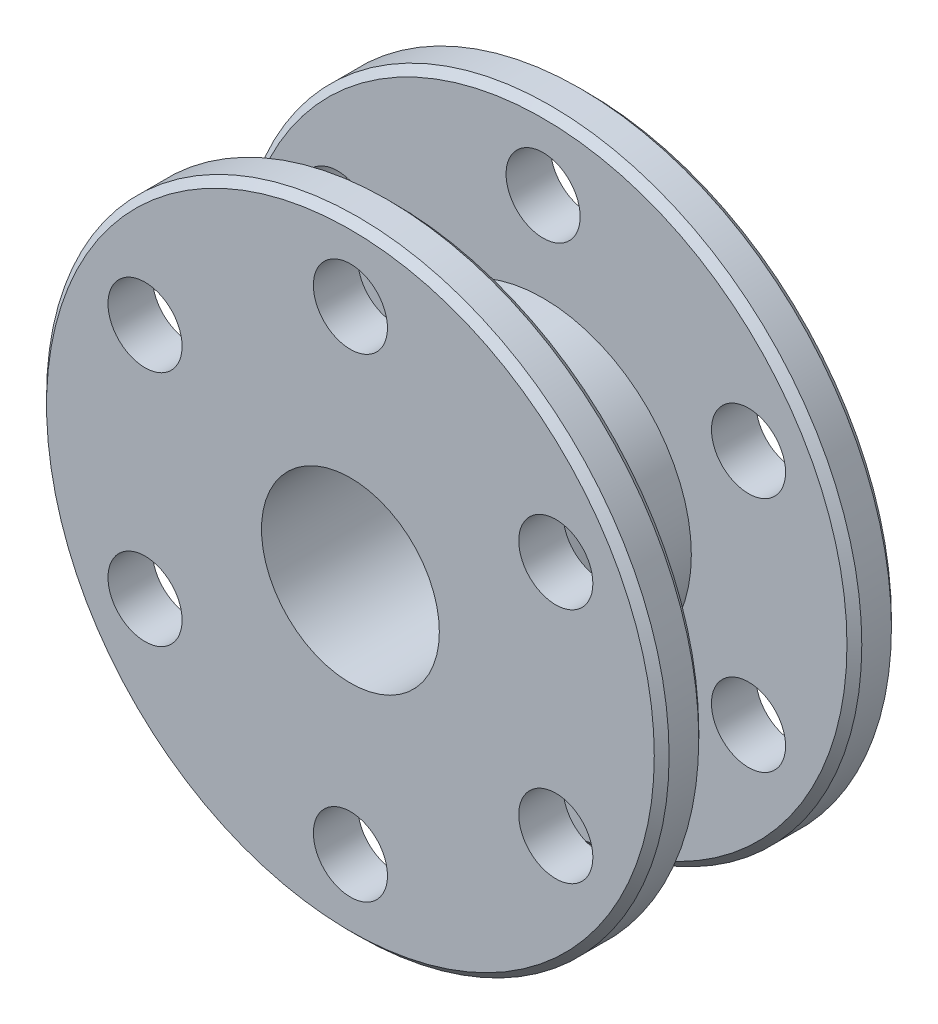
SolidWorks part; units mm, degrees
material "Brass"
ref_plane "Front Plane" through (0, 0, 0) normal (0, 0, 1) x (1, 0, 0)
ref_plane "Top Plane" through (0, 0, 0) normal (0, 1, 0) x (1, 0, 0)
ref_plane "Right Plane" through (0, 0, 0) normal (1, 0, 0) x (0, 0, -1)
sketch "Sketch1" plane through (0, 0, 0) normal (0, 0, 1) x (1, 0, 0)
  circle A0 centre (0, 0) radius 10.5
  dimension "D1" = 21
extrude "Boss-Extrude1" add sketch "Sketch1" along normal blind 4 and the other way blind 4
sketch "Sketch2" plane through (0, 0, 4) normal (0, 0, 1) x (1, 0, 0)
  circle A0 centre (0, 0) radius 3
  dimension "D1" = 6
extrude "Cut-Extrude1" cut sketch "Sketch2" against normal blind 10
chamfer "Chamfer1" distance 0.25 angle 45 1 edges at (10.5, 0, 4)
chamfer "Chamfer2" distance 0.25 angle 45 1 edges at (10.5, 0, -4)
sketch "Sketch3" plane through (0, 0, 4) normal (0, 0, 1) x (1, 0, 0)
  circle A0 centre (0, 0) radius 5
  dimension "D1" = 10
extrude "Cut-Extrude2" cut sketch "Sketch3" against normal blind 5 from offset 1.5 flip side to cut offset against normal yes
chamfer "Chamfer3" distance 0.25 angle 45 2 edges at (10.5, 0, -2.5) (10.5, 0, 2.5)
sketch "Sketch4" plane through (0, 0, 4) normal (0, 0, 1) x (1, 0, 0)
  line L0 (0, 11.5067) -> (0, -11.589) construction
  line L1 (0, 0) -> (0, 8) construction
  circle A0 centre (0, 0) radius 8 construction
  circle A1 centre (0, 8) radius 1.25
  circle A2 centre (6.9282, 4) radius 1.25
  circle A3 centre (6.9282, -4) radius 1.25
  circle A4 centre (0, -8) radius 1.25
  circle A5 centre (-6.9282, -4) radius 1.25
  circle A6 centre (-6.9282, 4) radius 1.25
  dimension "D1" = 16
  dimension "D2" = 2.5
  dimension "D5" = 8
  dimension "D4" = 8
  dimension "D3" = 6
extrude "Cut-Extrude3" cut sketch "Sketch4" against normal through all both and the other way through all
